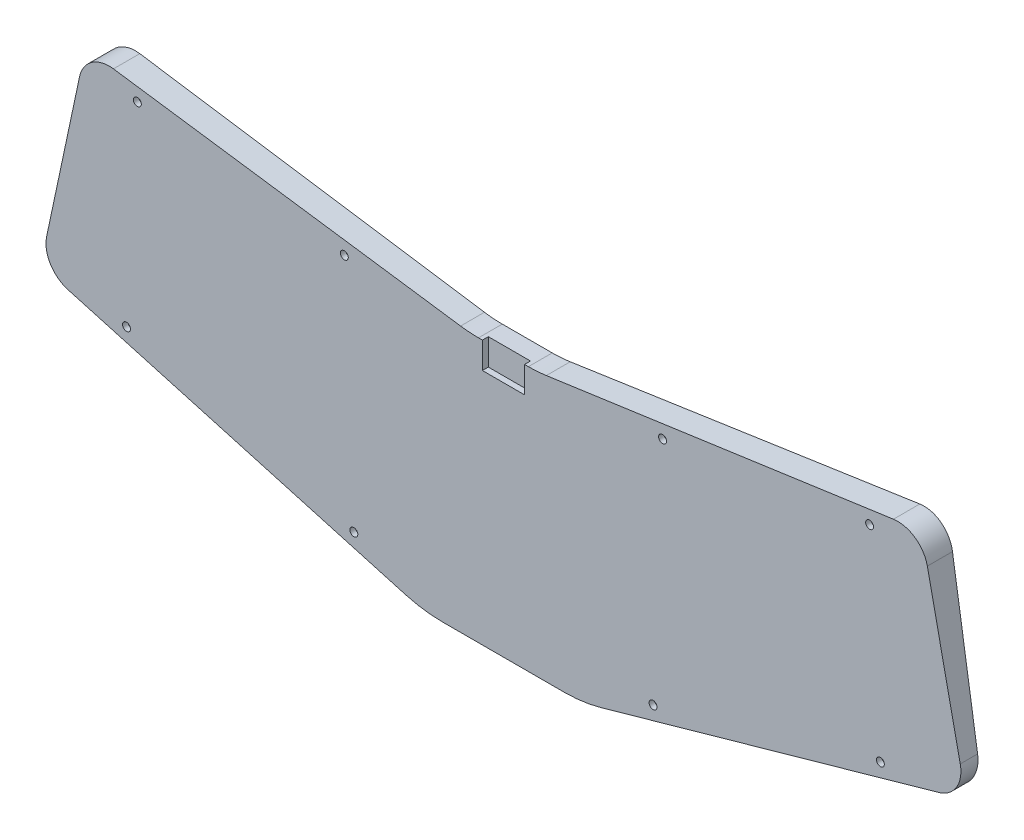
SolidWorks part; units mm, degrees
ref_plane "Front Plane" through (0, 0, 0) normal (0, 0, 1) x (1, 0, 0)
ref_plane "Top Plane" through (0, 0, 0) normal (0, 1, 0) x (1, 0, 0)
ref_plane "Right Plane" through (0, 0, 0) normal (1, 0, 0) x (0, 0, -1)
sketch "Model" plane through (0, 0, 0) normal (0, 0, 1) x (1, 0, 0)
  line L0 (7.1929, 63.9009) -> (19.4198, 61.302)
  line L1 (19.9974, 60.4125) -> (17.3986, 48.1856)
  line L2 (16.509, 47.6079) -> (4.2822, 50.2068)
  line L3 (3.7045, 51.0964) -> (6.3034, 63.3232)
  line L4 (3.2426, 45.3161) -> (15.4694, 42.7172)
  line L5 (16.0471, 41.8276) -> (13.4482, 29.6008)
  line L6 (12.5587, 29.0231) -> (0.3318, 31.622)
  line L7 (-0.2458, 32.5116) -> (2.3531, 44.7384)
  line L8 (-0.7077, 26.7313) -> (11.5191, 24.1324)
  line L9 (12.0968, 23.2428) -> (9.4979, 11.016)
  line L10 (8.6084, 10.4383) -> (-3.6185, 13.0372)
  line L11 (-4.1962, 13.9268) -> (-1.5973, 26.1536)
  line L12 (26.1936, 61.9069) -> (38.4204, 59.308)
  line L13 (38.9981, 58.4184) -> (36.3992, 46.1916)
  line L14 (35.5096, 45.6139) -> (23.2828, 48.2128)
  line L15 (22.7051, 49.1023) -> (25.304, 61.3292)
  line L16 (22.2432, 43.3221) -> (34.4701, 40.7232)
  line L17 (35.0478, 39.8336) -> (32.4489, 27.6068)
  line L18 (31.5593, 27.0291) -> (19.3325, 29.628)
  line L19 (18.7548, 30.5175) -> (21.3537, 42.7444)
  line L20 (18.2929, 24.7373) -> (30.5198, 22.1384)
  line L21 (31.0974, 21.2488) -> (28.4985, 9.022)
  line L22 (27.609, 8.4443) -> (15.3821, 11.0432)
  line L23 (14.8045, 11.9327) -> (17.4034, 24.1596)
  line L24 (45.2981, 60.4019) -> (57.525, 57.803)
  line L25 (58.1027, 56.9135) -> (55.5038, 44.6866)
  line L26 (54.6142, 44.109) -> (42.3874, 46.7078)
  line L27 (41.8097, 47.5974) -> (44.4086, 59.8242)
  line L28 (41.3478, 41.8171) -> (53.5747, 39.2182)
  line L29 (54.1523, 38.3287) -> (51.5534, 26.1018)
  line L30 (50.6639, 25.5241) -> (38.4371, 28.123)
  line L31 (37.8594, 29.0126) -> (40.4583, 41.2394)
  line L32 (37.3975, 23.2323) -> (49.6243, 20.6334)
  line L33 (50.202, 19.7439) -> (47.6031, 7.517)
  line L34 (46.7136, 6.9393) -> (34.4867, 9.5382)
  line L35 (33.9091, 10.4278) -> (36.5079, 22.6546)
  line L36 (64.4027, 58.897) -> (76.6296, 56.2981)
  line L37 (77.2072, 55.4085) -> (74.6083, 43.1817)
  line L38 (73.7188, 42.604) -> (61.492, 45.2029)
  line L39 (60.9143, 46.0924) -> (63.5132, 58.3193)
  line L40 (60.4524, 40.3122) -> (72.6792, 37.7133)
  line L41 (73.2569, 36.8237) -> (70.658, 24.5969)
  line L42 (69.7685, 24.0192) -> (57.5416, 26.6181)
  line L43 (56.964, 27.5076) -> (59.5629, 39.7345)
  line L44 (56.5021, 21.7274) -> (68.7289, 19.1285)
  line L45 (69.3066, 18.2389) -> (66.7077, 6.0121)
  line L46 (65.8182, 5.4344) -> (53.5913, 8.0333)
  line L47 (53.0136, 8.9228) -> (55.6125, 21.1497)
  line L48 (52.5518, 3.1425) -> (64.7786, 0.5437)
  line L49 (65.3563, -0.3459) -> (62.7574, -12.5727)
  line L50 (61.8678, -13.1504) -> (49.641, -10.5515)
  line L51 (49.0633, -9.662) -> (51.6622, 2.5649)
  line L52 (82.4677, 52.5013) -> (94.6946, 49.9024)
  line L53 (95.2723, 49.0128) -> (92.6734, 36.786)
  line L54 (91.7838, 36.2083) -> (79.557, 38.8072)
  line L55 (78.9793, 39.6967) -> (81.5782, 51.9236)
  line L56 (78.5174, 33.9165) -> (90.7443, 31.3176)
  line L57 (91.3219, 30.428) -> (88.723, 18.2012)
  line L58 (87.8335, 17.6235) -> (75.6067, 20.2224)
  line L59 (75.029, 21.1119) -> (77.6279, 33.3388)
  line L60 (74.5671, 15.3317) -> (86.7939, 12.7328)
  line L61 (87.3716, 11.8432) -> (84.7727, -0.3836)
  line L62 (83.8832, -0.9613) -> (71.6563, 1.6376)
  line L63 (71.0787, 2.5271) -> (73.6776, 14.754)
  line L64 (101.4684, 50.5072) -> (113.6952, 47.9083)
  line L65 (114.2729, 47.0188) -> (111.674, 34.792)
  line L66 (110.7845, 34.2143) -> (98.5576, 36.8132)
  line L67 (97.9799, 37.7027) -> (100.5788, 49.9296)
  line L68 (97.5181, 31.9224) -> (109.7449, 29.3235)
  line L69 (110.3226, 28.434) -> (107.7237, 16.2072)
  line L70 (106.8341, 15.6295) -> (94.6073, 18.2284)
  line L71 (94.0296, 19.1179) -> (96.6285, 31.3448)
  line L72 (93.5677, 13.3376) -> (105.7946, 10.7387)
  line L73 (106.3723, 9.8492) -> (103.7734, -2.3777)
  line L74 (102.8838, -2.9553) -> (90.657, -0.3564)
  line L75 (90.0793, 0.5331) -> (92.6782, 12.76)
  line L76 (134.1052, 48.9374) -> (131.5063, 36.7105)
  line L77 (130.6167, 36.1328) -> (118.3899, 38.7317)
  line L78 (117.8122, 39.6213) -> (120.4111, 51.8481)
  line L79 (117.3503, 33.841) -> (129.5772, 31.2421)
  line L80 (130.1548, 30.3526) -> (127.556, 18.1257)
  line L81 (126.6664, 17.548) -> (114.4396, 20.1469)
  line L82 (113.8619, 21.0365) -> (116.4608, 33.2633)
  line L83 (113.4, 15.2562) -> (125.6268, 12.6573)
  line L84 (126.2045, 11.7678) -> (123.6056, -0.4591)
  line L85 (122.7161, -1.0368) -> (110.4892, 1.5621)
  line L86 (109.9116, 2.4517) -> (112.5105, 14.6785)
  line L87 (70.6168, -3.2531) -> (82.8436, -5.852)
  line L88 (83.4213, -6.7416) -> (80.8224, -18.9684)
  line L89 (79.9329, -19.5461) -> (67.706, -16.9472)
  line L90 (67.1283, -16.0577) -> (69.7272, -3.8308)
  line L91 (89.6174, -5.2472) -> (101.8443, -7.8461)
  line L92 (102.4219, -8.7356) -> (99.823, -20.9625)
  line L93 (98.9335, -21.5401) -> (86.7066, -18.9412)
  line L94 (86.129, -18.0517) -> (88.7279, -5.8248)
  line L95 (117.654, -29.3648) -> (112.0852, -26.5274)
  line L96 (111.7574, -25.5186) -> (117.4323, -14.381)
  line L97 (118.4411, -14.0533) -> (129.5787, -19.7282)
  line L98 (129.9064, -20.7369) -> (124.2315, -31.8745)
  line L99 (123.2228, -32.2023) -> (117.654, -29.3648)
  line L100 (112.629, -33.5493) -> (124.2783, -36.8388)
  line L101 (137.0504, -38.6074) -> (160.1264, -38.6074)
  line L102 (160.1264, -38.6074) -> (183.2025, -38.6074)
  line L103 (195.9746, -36.8388) -> (207.6239, -33.5493)
  line L104 (226.4824, -28.2242) -> (271.949, -15.3856)
  line L105 (271.949, -15.3856) -> (293.9202, -9.1816)
  line L106 (210.7632, 57.9332) -> (177.0346, 53.1572)
  line L107 (169.604, 52.6338) -> (150.6488, 52.6338)
  line L108 (143.2182, 53.1572) -> (109.4896, 57.9332)
  line L109 (90.0873, 60.6806) -> (30.9176, 69.0589)
  line L110 (289.3352, 69.0589) -> (230.1656, 60.6806)
  line L111 (26.3327, -9.1816) -> (48.3039, -15.3856)
  line L112 (48.3039, -15.3856) -> (93.7705, -28.2242)
  line L113 (312.7787, -3.8564) -> (324.1811, -0.6367)
  line L114 (-2.1254, 39.3007) -> (3.622, 66.34)
  line L115 (-2.1254, 39.3007) -> (-8.8731, 7.5553)
  line L116 (13.8071, 71.4818) -> (11.4504, 71.8155)
  line L117 (-3.9283, -0.6367) -> (7.4742, -3.8564)
  line L118 (306.4458, 71.4818) -> (308.8024, 71.8155)
  line L119 (322.3782, 39.3007) -> (329.1259, 7.5553)
  line L120 (322.3782, 39.3007) -> (316.6308, 66.34)
  line L121 (121.3006, 52.4258) -> (133.5275, 49.8269)
  line L122 (313.0599, 63.9009) -> (300.8331, 61.302)
  line L123 (300.2554, 60.4125) -> (302.8543, 48.1856)
  line L124 (303.7438, 47.6079) -> (315.9707, 50.2068)
  line L125 (316.5483, 51.0964) -> (313.9494, 63.3232)
  line L126 (317.0102, 45.3161) -> (304.7834, 42.7172)
  line L127 (304.2057, 41.8276) -> (306.8046, 29.6008)
  line L128 (307.6941, 29.0231) -> (319.921, 31.622)
  line L129 (320.4987, 32.5116) -> (317.8998, 44.7384)
  line L130 (320.9605, 26.7313) -> (308.7337, 24.1324)
  line L131 (308.156, 23.2428) -> (310.7549, 11.016)
  line L132 (311.6445, 10.4383) -> (323.8713, 13.0372)
  line L133 (324.449, 13.9268) -> (321.8501, 26.1536)
  line L134 (294.0593, 61.9069) -> (281.8324, 59.308)
  line L135 (281.2548, 58.4184) -> (283.8536, 46.1916)
  line L136 (284.7432, 45.6139) -> (296.97, 48.2128)
  line L137 (297.5477, 49.1023) -> (294.9488, 61.3292)
  line L138 (298.0096, 43.3221) -> (285.7828, 40.7232)
  line L139 (285.2051, 39.8336) -> (287.804, 27.6068)
  line L140 (288.6935, 27.0291) -> (300.9204, 29.628)
  line L141 (301.498, 30.5175) -> (298.8991, 42.7444)
  line L142 (301.9599, 24.7373) -> (289.7331, 22.1384)
  line L143 (289.1554, 21.2488) -> (291.7543, 9.022)
  line L144 (292.6438, 8.4443) -> (304.8707, 11.0432)
  line L145 (305.4484, 11.9327) -> (302.8495, 24.1596)
  line L146 (274.9547, 60.4019) -> (262.7278, 57.803)
  line L147 (262.1502, 56.9135) -> (264.7491, 44.6866)
  line L148 (265.6386, 44.109) -> (277.8655, 46.7078)
  line L149 (278.4431, 47.5974) -> (275.8442, 59.8242)
  line L150 (278.905, 41.8171) -> (266.6782, 39.2182)
  line L151 (266.1005, 38.3287) -> (268.6994, 26.1018)
  line L152 (269.5889, 25.5241) -> (281.8158, 28.123)
  line L153 (282.3935, 29.0126) -> (279.7946, 41.2394)
  line L154 (282.8553, 23.2323) -> (270.6285, 20.6334)
  line L155 (270.0508, 19.7439) -> (272.6497, 7.517)
  line L156 (273.5393, 6.9393) -> (285.7661, 9.5382)
  line L157 (286.3438, 10.4278) -> (283.7449, 22.6546)
  line L158 (255.8501, 58.897) -> (243.6233, 56.2981)
  line L159 (243.0456, 55.4085) -> (245.6445, 43.1817)
  line L160 (246.534, 42.604) -> (258.7609, 45.2029)
  line L161 (259.3385, 46.0924) -> (256.7397, 58.3193)
  line L162 (259.8004, 40.3122) -> (247.5736, 37.7133)
  line L163 (246.9959, 36.8237) -> (249.5948, 24.5969)
  line L164 (250.4843, 24.0192) -> (262.7112, 26.6181)
  line L165 (263.2889, 27.5076) -> (260.69, 39.7345)
  line L166 (263.7508, 21.7274) -> (251.5239, 19.1285)
  line L167 (250.9462, 18.2389) -> (253.5451, 6.0121)
  line L168 (254.4347, 5.4344) -> (266.6615, 8.0333)
  line L169 (267.2392, 8.9228) -> (264.6403, 21.1497)
  line L170 (267.7011, 3.1425) -> (255.4742, 0.5437)
  line L171 (254.8966, -0.3459) -> (257.4954, -12.5727)
  line L172 (258.385, -13.1504) -> (270.6118, -10.5515)
  line L173 (271.1895, -9.662) -> (268.5906, 2.5649)
  line L174 (237.7851, 52.5013) -> (225.5582, 49.9024)
  line L175 (224.9806, 49.0128) -> (227.5795, 36.786)
  line L176 (228.469, 36.2083) -> (240.6958, 38.8072)
  line L177 (241.2735, 39.6967) -> (238.6746, 51.9236)
  line L178 (241.7354, 33.9165) -> (229.5086, 31.3176)
  line L179 (228.9309, 30.428) -> (231.5298, 18.2012)
  line L180 (232.4193, 17.6235) -> (244.6462, 20.2224)
  line L181 (245.2238, 21.1119) -> (242.6249, 33.3388)
  line L182 (245.6857, 15.3317) -> (233.4589, 12.7328)
  line L183 (232.8812, 11.8432) -> (235.4801, -0.3836)
  line L184 (236.3696, -0.9613) -> (248.5965, 1.6376)
  line L185 (249.1742, 2.5271) -> (246.5753, 14.754)
  line L186 (218.7845, 50.5072) -> (206.5576, 47.9083)
  line L187 (205.9799, 47.0188) -> (208.5788, 34.792)
  line L188 (209.4684, 34.2143) -> (221.6952, 36.8132)
  line L189 (222.2729, 37.7027) -> (219.674, 49.9296)
  line L190 (222.7348, 31.9224) -> (210.5079, 29.3235)
  line L191 (209.9303, 28.434) -> (212.5292, 16.2072)
  line L192 (213.4187, 15.6295) -> (225.6455, 18.2284)
  line L193 (226.2232, 19.1179) -> (223.6243, 31.3448)
  line L194 (226.6851, 13.3376) -> (214.4583, 10.7387)
  line L195 (213.8806, 9.8492) -> (216.4795, -2.3777)
  line L196 (217.369, -2.9553) -> (229.5959, -0.3564)
  line L197 (230.1735, 0.5331) -> (227.5746, 12.76)
  line L198 (186.1477, 48.9374) -> (188.7466, 36.7105)
  line L199 (189.6361, 36.1328) -> (201.8629, 38.7317)
  line L200 (202.4406, 39.6213) -> (199.8417, 51.8481)
  line L201 (202.9025, 33.841) -> (190.6757, 31.2421)
  line L202 (190.098, 30.3526) -> (192.6969, 18.1257)
  line L203 (193.5864, 17.548) -> (205.8133, 20.1469)
  line L204 (206.3909, 21.0365) -> (203.792, 33.2633)
  line L205 (206.8528, 15.2562) -> (194.626, 12.6573)
  line L206 (194.0483, 11.7678) -> (196.6472, -0.4591)
  line L207 (197.5367, -1.0368) -> (209.7636, 1.5621)
  line L208 (210.3413, 2.4517) -> (207.7424, 14.6785)
  line L209 (249.636, -3.2531) -> (237.4092, -5.852)
  line L210 (236.8315, -6.7416) -> (239.4304, -18.9684)
  line L211 (240.32, -19.5461) -> (252.5468, -16.9472)
  line L212 (253.1245, -16.0577) -> (250.5256, -3.8308)
  line L213 (230.6354, -5.2472) -> (218.4086, -7.8461)
  line L214 (217.8309, -8.7356) -> (220.4298, -20.9625)
  line L215 (221.3193, -21.5401) -> (233.5462, -18.9412)
  line L216 (234.1239, -18.0517) -> (231.525, -5.8248)
  line L217 (202.5988, -29.3648) -> (208.1676, -26.5274)
  line L218 (208.4954, -25.5186) -> (202.8205, -14.381)
  line L219 (201.8118, -14.0533) -> (190.6742, -19.7282)
  line L220 (190.3464, -20.7369) -> (196.0213, -31.8745)
  line L221 (197.03, -32.2023) -> (202.5988, -29.3648)
  line L222 (198.9522, 52.4258) -> (186.7253, 49.8269)
  line L223 (169.604, 55.6338) -> (150.6488, 55.6338)
  line L224 (143.6388, 56.1276) -> (11.8711, 74.7858)
  line L225 (0.6876, 66.9637) -> (-5.0598, 39.9244)
  line L226 (-5.0598, 39.9244) -> (-11.8075, 8.179)
  line L227 (-4.7435, -3.5238) -> (47.4886, -18.2727)
  line L228 (47.4886, -18.2727) -> (123.463, -39.7259)
  line L229 (137.0504, -41.6074) -> (160.1264, -41.6074)
  line L230 (160.1264, -41.6074) -> (183.2025, -41.6074)
  line L231 (196.7898, -39.7259) -> (272.7642, -18.2727)
  line L232 (272.7642, -18.2727) -> (324.9963, -3.5238)
  line L233 (332.0603, 8.179) -> (325.3126, 39.9244)
  line L234 (325.3126, 39.9244) -> (319.5653, 66.9637)
  line L235 (308.3818, 74.7858) -> (176.614, 56.1276)
  line L236 (169.604, 57.1338) -> (150.6488, 57.1338)
  line L237 (143.8491, 57.6128) -> (12.0814, 76.271)
  line L238 (-0.7797, 67.2756) -> (-6.527, 40.2363)
  line L239 (-6.527, 40.2363) -> (-13.2747, 8.4909)
  line L240 (-5.1511, -4.9673) -> (47.081, -19.7163)
  line L241 (47.081, -19.7163) -> (123.0554, -41.1694)
  line L242 (137.0504, -43.1074) -> (160.1264, -43.1074)
  line L243 (160.1264, -43.1074) -> (183.2025, -43.1074)
  line L244 (197.1974, -41.1694) -> (273.1718, -19.7163)
  line L245 (273.1718, -19.7163) -> (325.404, -4.9673)
  line L246 (333.5276, 8.4909) -> (326.7799, 40.2363)
  line L247 (326.7799, 40.2363) -> (321.0325, 67.2756)
  line L248 (308.1715, 76.271) -> (176.4037, 57.6128)
  arc A0 (106.6702, -28.8979) -> (101.2821, -27.3764) centre (103.1997, -30.8868) ccw
  arc A1 (93.7705, -28.2242) -> (101.2821, -27.3764) centre (96.4879, -18.6005) ccw
  arc A2 (106.6702, -28.8979) -> (112.629, -33.5493) centre (115.3464, -23.9256) ccw
  circle A3 centre (103.3356, -30.4056) radius 1.5
  arc A4 (207.6239, -33.5493) -> (213.5826, -28.8979) centre (204.9064, -23.9256) ccw
  arc A5 (218.9708, -27.3764) -> (226.4824, -28.2242) centre (223.7649, -18.6005) ccw
  arc A6 (218.9708, -27.3764) -> (213.5826, -28.8979) centre (217.0531, -30.8868) ccw
  circle A7 centre (216.9173, -30.4056) radius 1.5
  arc A8 (218.0932, 56.0855) -> (223.6367, 56.8704) centre (220.4644, 59.3069) ccw
  arc A9 (96.6161, 56.8704) -> (102.1596, 56.0855) centre (99.7884, 59.3069) ccw
  arc A10 (109.4896, 57.9332) -> (102.1596, 56.0855) centre (108.0876, 48.032) ccw
  arc A11 (96.6161, 56.8704) -> (90.0873, 60.6806) centre (88.6852, 50.7793) ccw
  arc A12 (218.0932, 56.0855) -> (210.7632, 57.9332) centre (212.1652, 48.032) ccw
  arc A13 (230.1656, 60.6806) -> (223.6367, 56.8704) centre (231.5676, 50.7793) ccw
  circle A14 centre (99.7183, 58.8118) radius 1.5
  circle A15 centre (220.5345, 58.8118) radius 1.5
  arc A16 (305.2671, -3.0086) -> (299.8789, -4.5301) centre (303.3494, -6.519) ccw
  arc A17 (20.3739, -4.5301) -> (14.9858, -3.0086) centre (16.9034, -6.519) ccw
  arc A18 (20.3739, -4.5301) -> (26.3327, -9.1816) centre (29.0501, 0.4421) ccw
  arc A19 (305.2671, -3.0086) -> (312.7787, -3.8564) centre (310.0612, 5.7673) ccw
  arc A20 (293.9202, -9.1816) -> (299.8789, -4.5301) centre (291.2027, 0.4421) ccw
  arc A21 (7.4742, -3.8564) -> (14.9858, -3.0086) centre (10.1916, 5.7673) ccw
  circle A22 centre (17.0393, -6.0378) radius 1.5
  circle A23 centre (303.2135, -6.0378) radius 1.5
  arc A24 (-8.8731, 7.5553) -> (-3.9283, -0.6367) centre (-2.026, 6.0999) ccw
  arc A25 (11.4504, 71.8155) -> (3.622, 66.34) centre (10.469, 64.8846) ccw
  arc A26 (316.6308, 66.34) -> (308.8024, 71.8155) centre (309.7838, 64.8846) ccw
  arc A27 (324.1811, -0.6367) -> (329.1259, 7.5553) centre (322.2789, 6.0999) ccw
  arc A28 (296.6652, 67.2112) -> (302.641, 68.6986) centre (299.0364, 70.4326) ccw
  arc A29 (17.6118, 68.6986) -> (23.5876, 67.2112) centre (21.2165, 70.4326) ccw
  arc A30 (30.9176, 69.0589) -> (23.5876, 67.2112) centre (29.5156, 59.1577) ccw
  arc A31 (17.6118, 68.6986) -> (13.8071, 71.4818) centre (13.106, 66.5312) ccw
  arc A32 (306.4458, 71.4818) -> (302.641, 68.6986) centre (307.1468, 66.5312) ccw
  arc A33 (296.6652, 67.2112) -> (289.3352, 69.0589) centre (290.7372, 59.1577) ccw
  circle A34 centre (299.1065, 69.9376) radius 1.5
  circle A35 centre (21.1464, 69.9376) radius 1.5
  arc A36 (3.7045, 51.0964) -> (4.2822, 50.2068) centre (4.4381, 50.9404) ccw
  arc A37 (7.1929, 63.9009) -> (6.3034, 63.3232) centre (7.037, 63.1673) ccw
  arc A38 (19.9974, 60.4125) -> (19.4198, 61.302) centre (19.2638, 60.5684) ccw
  arc A39 (16.509, 47.6079) -> (17.3986, 48.1856) centre (16.6649, 48.3415) ccw
  arc A40 (3.2426, 45.3161) -> (2.3531, 44.7384) centre (3.0867, 44.5825) ccw
  arc A41 (-0.2458, 32.5116) -> (0.3318, 31.622) centre (0.4878, 32.3556) ccw
  arc A42 (12.5587, 29.0231) -> (13.4482, 29.6008) centre (12.7146, 29.7567) ccw
  arc A43 (16.0471, 41.8276) -> (15.4694, 42.7172) centre (15.3135, 41.9836) ccw
  arc A44 (-0.7077, 26.7313) -> (-1.5973, 26.1536) centre (-0.8637, 25.9977) ccw
  arc A45 (-4.1962, 13.9268) -> (-3.6185, 13.0372) centre (-3.4625, 13.7708) ccw
  arc A46 (8.6084, 10.4383) -> (9.4979, 11.016) centre (8.7643, 11.1719) ccw
  arc A47 (12.0968, 23.2428) -> (11.5191, 24.1324) centre (11.3632, 23.3988) ccw
  arc A48 (14.8045, 11.9327) -> (15.3821, 11.0432) centre (15.5381, 11.7768) ccw
  arc A49 (27.609, 8.4443) -> (28.4985, 9.022) centre (27.7649, 9.1779) ccw
  arc A50 (31.0974, 21.2488) -> (30.5198, 22.1384) centre (30.3638, 21.4048) ccw
  arc A51 (18.2929, 24.7373) -> (17.4034, 24.1596) centre (18.137, 24.0036) ccw
  arc A52 (18.7548, 30.5175) -> (19.3325, 29.628) centre (19.4884, 30.3616) ccw
  arc A53 (31.5593, 27.0291) -> (32.4489, 27.6068) centre (31.7152, 27.7627) ccw
  arc A54 (35.0478, 39.8336) -> (34.4701, 40.7232) centre (34.3141, 39.9896) ccw
  arc A55 (22.2432, 43.3221) -> (21.3537, 42.7444) centre (22.0873, 42.5885) ccw
  arc A56 (22.7051, 49.1023) -> (23.2828, 48.2128) centre (23.4387, 48.9464) ccw
  arc A57 (35.5096, 45.6139) -> (36.3992, 46.1916) centre (35.6656, 46.3475) ccw
  arc A58 (38.9981, 58.4184) -> (38.4204, 59.308) centre (38.2645, 58.5744) ccw
  arc A59 (26.1936, 61.9069) -> (25.304, 61.3292) centre (26.0376, 61.1733) ccw
  arc A60 (33.9091, 10.4278) -> (34.4867, 9.5382) centre (34.6427, 10.2718) ccw
  arc A61 (37.3975, 23.2323) -> (36.5079, 22.6546) centre (37.2416, 22.4987) ccw
  arc A62 (50.202, 19.7439) -> (49.6243, 20.6334) centre (49.4684, 19.8998) ccw
  arc A63 (46.7136, 6.9393) -> (47.6031, 7.517) centre (46.8695, 7.673) ccw
  arc A64 (50.6639, 25.5241) -> (51.5534, 26.1018) centre (50.8198, 26.2578) ccw
  arc A65 (37.8594, 29.0126) -> (38.4371, 28.123) centre (38.593, 28.8567) ccw
  arc A66 (41.3478, 41.8171) -> (40.4583, 41.2394) centre (41.1919, 41.0835) ccw
  arc A67 (54.1523, 38.3287) -> (53.5747, 39.2182) centre (53.4187, 38.4846) ccw
  arc A68 (54.6142, 44.109) -> (55.5038, 44.6866) centre (54.7702, 44.8426) ccw
  arc A69 (41.8097, 47.5974) -> (42.3874, 46.7078) centre (42.5433, 47.4415) ccw
  arc A70 (45.2981, 60.4019) -> (44.4086, 59.8242) centre (45.1422, 59.6683) ccw
  arc A71 (58.1027, 56.9135) -> (57.525, 57.803) centre (57.369, 57.0694) ccw
  arc A72 (56.964, 27.5076) -> (57.5416, 26.6181) centre (57.6976, 27.3517) ccw
  arc A73 (60.4524, 40.3122) -> (59.5629, 39.7345) centre (60.2965, 39.5785) ccw
  arc A74 (73.2569, 36.8237) -> (72.6792, 37.7133) centre (72.5233, 36.9797) ccw
  arc A75 (69.7685, 24.0192) -> (70.658, 24.5969) centre (69.9244, 24.7528) ccw
  arc A76 (60.9143, 46.0924) -> (61.492, 45.2029) centre (61.6479, 45.9365) ccw
  arc A77 (73.7188, 42.604) -> (74.6083, 43.1817) centre (73.8747, 43.3376) ccw
  arc A78 (77.2072, 55.4085) -> (76.6296, 56.2981) centre (76.4736, 55.5645) ccw
  arc A79 (64.4027, 58.897) -> (63.5132, 58.3193) centre (64.2468, 58.1634) ccw
  arc A80 (53.0136, 8.9228) -> (53.5913, 8.0333) centre (53.7472, 8.7669) ccw
  arc A81 (56.5021, 21.7274) -> (55.6125, 21.1497) centre (56.3461, 20.9937) ccw
  arc A82 (69.3066, 18.2389) -> (68.7289, 19.1285) centre (68.573, 18.3948) ccw
  arc A83 (65.8182, 5.4344) -> (66.7077, 6.0121) centre (65.9741, 6.168) ccw
  arc A84 (49.0633, -9.662) -> (49.641, -10.5515) centre (49.7969, -9.8179) ccw
  arc A85 (52.5518, 3.1425) -> (51.6622, 2.5649) centre (52.3958, 2.4089) ccw
  arc A86 (65.3563, -0.3459) -> (64.7786, 0.5437) centre (64.6227, -0.19) ccw
  arc A87 (61.8678, -13.1504) -> (62.7574, -12.5727) centre (62.0238, -12.4168) ccw
  arc A88 (67.1283, -16.0577) -> (67.706, -16.9472) centre (67.8619, -16.2136) ccw
  arc A89 (70.6168, -3.2531) -> (69.7272, -3.8308) centre (70.4608, -3.9868) ccw
  arc A90 (83.4213, -6.7416) -> (82.8436, -5.852) centre (82.6877, -6.5856) ccw
  arc A91 (79.9329, -19.5461) -> (80.8224, -18.9684) centre (80.0888, -18.8125) ccw
  arc A92 (71.0787, 2.5271) -> (71.6563, 1.6376) centre (71.8123, 2.3712) ccw
  arc A93 (83.8832, -0.9613) -> (84.7727, -0.3836) centre (84.0391, -0.2277) ccw
  arc A94 (87.3716, 11.8432) -> (86.7939, 12.7328) centre (86.638, 11.9992) ccw
  arc A95 (74.5671, 15.3317) -> (73.6776, 14.754) centre (74.4112, 14.5981) ccw
  arc A96 (75.029, 21.1119) -> (75.6067, 20.2224) centre (75.7626, 20.956) ccw
  arc A97 (87.8335, 17.6235) -> (88.723, 18.2012) centre (87.9894, 18.3571) ccw
  arc A98 (91.3219, 30.428) -> (90.7443, 31.3176) centre (90.5883, 30.584) ccw
  arc A99 (78.5174, 33.9165) -> (77.6279, 33.3388) centre (78.3615, 33.1829) ccw
  arc A100 (78.9793, 39.6967) -> (79.557, 38.8072) centre (79.7129, 39.5408) ccw
  arc A101 (82.4677, 52.5013) -> (81.5782, 51.9236) centre (82.3118, 51.7677) ccw
  arc A102 (95.2723, 49.0128) -> (94.6946, 49.9024) centre (94.5387, 49.1688) ccw
  arc A103 (91.7838, 36.2083) -> (92.6734, 36.786) centre (91.9398, 36.9419) ccw
  arc A104 (97.9799, 37.7027) -> (98.5576, 36.8132) centre (98.7135, 37.5468) ccw
  arc A105 (101.4684, 50.5072) -> (100.5788, 49.9296) centre (101.3124, 49.7736) ccw
  arc A106 (114.2729, 47.0188) -> (113.6952, 47.9083) centre (113.5393, 47.1747) ccw
  arc A107 (110.7845, 34.2143) -> (111.674, 34.792) centre (110.9404, 34.9479) ccw
  arc A108 (97.5181, 31.9224) -> (96.6285, 31.3448) centre (97.3621, 31.1888) ccw
  arc A109 (110.3226, 28.434) -> (109.7449, 29.3235) centre (109.589, 28.5899) ccw
  arc A110 (106.8341, 15.6295) -> (107.7237, 16.2072) centre (106.9901, 16.3631) ccw
  arc A111 (94.0296, 19.1179) -> (94.6073, 18.2284) centre (94.7632, 18.962) ccw
  arc A112 (93.5677, 13.3376) -> (92.6782, 12.76) centre (93.4118, 12.604) ccw
  arc A113 (106.3723, 9.8492) -> (105.7946, 10.7387) centre (105.6386, 10.0051) ccw
  arc A114 (102.8838, -2.9553) -> (103.7734, -2.3777) centre (103.0397, -2.2217) ccw
  arc A115 (90.0793, 0.5331) -> (90.657, -0.3564) centre (90.8129, 0.3772) ccw
  arc A116 (89.6174, -5.2472) -> (88.7279, -5.8248) centre (89.4615, -5.9808) ccw
  arc A117 (102.4219, -8.7356) -> (101.8443, -7.8461) centre (101.6883, -8.5797) ccw
  arc A118 (98.9335, -21.5401) -> (99.823, -20.9625) centre (99.0894, -20.8065) ccw
  arc A119 (86.129, -18.0517) -> (86.7066, -18.9412) centre (86.8626, -18.2076) ccw
  arc A120 (111.7574, -25.5186) -> (112.0852, -26.5274) centre (112.4257, -25.8591) ccw
  arc A121 (118.4411, -14.0533) -> (117.4323, -14.381) centre (118.1006, -14.7215) ccw
  arc A122 (129.9064, -20.7369) -> (129.5787, -19.7282) centre (129.2382, -20.3964) ccw
  arc A123 (123.2228, -32.2023) -> (124.2315, -31.8745) centre (123.5633, -31.534) ccw
  arc A124 (109.9116, 2.4517) -> (110.4892, 1.5621) centre (110.6452, 2.2957) ccw
  arc A125 (122.7161, -1.0368) -> (123.6056, -0.4591) centre (122.872, -0.3032) ccw
  arc A126 (126.2045, 11.7678) -> (125.6268, 12.6573) centre (125.4709, 11.9237) ccw
  arc A127 (113.4, 15.2562) -> (112.5105, 14.6785) centre (113.2441, 14.5226) ccw
  arc A128 (113.8619, 21.0365) -> (114.4396, 20.1469) centre (114.5955, 20.8805) ccw
  arc A129 (126.6664, 17.548) -> (127.556, 18.1257) centre (126.8223, 18.2817) ccw
  arc A130 (130.1548, 30.3526) -> (129.5772, 31.2421) centre (129.4212, 30.5085) ccw
  arc A131 (117.3503, 33.841) -> (116.4608, 33.2633) centre (117.1944, 33.1074) ccw
  arc A132 (117.8122, 39.6213) -> (118.3899, 38.7317) centre (118.5458, 39.4654) ccw
  arc A133 (130.6167, 36.1328) -> (131.5063, 36.7105) centre (130.7727, 36.8665) ccw
  arc A134 (134.1052, 48.9374) -> (133.5275, 49.8269) centre (133.3716, 49.0933) ccw
  arc A135 (121.3006, 52.4258) -> (120.4111, 51.8481) centre (121.1447, 51.6922) ccw
  arc A136 (313.9494, 63.3232) -> (313.0599, 63.9009) centre (313.2158, 63.1673) ccw
  arc A137 (300.8331, 61.302) -> (300.2554, 60.4125) centre (300.989, 60.5684) ccw
  arc A138 (302.8543, 48.1856) -> (303.7438, 47.6079) centre (303.5879, 48.3415) ccw
  arc A139 (315.9707, 50.2068) -> (316.5483, 51.0964) centre (315.8147, 50.9404) ccw
  arc A140 (317.8998, 44.7384) -> (317.0102, 45.3161) centre (317.1662, 44.5825) ccw
  arc A141 (304.7834, 42.7172) -> (304.2057, 41.8276) centre (304.9393, 41.9836) ccw
  arc A142 (306.8046, 29.6008) -> (307.6941, 29.0231) centre (307.5382, 29.7567) ccw
  arc A143 (319.921, 31.622) -> (320.4987, 32.5116) centre (319.7651, 32.3556) ccw
  arc A144 (321.8501, 26.1536) -> (320.9605, 26.7313) centre (321.1165, 25.9977) ccw
  arc A145 (308.7337, 24.1324) -> (308.156, 23.2428) centre (308.8896, 23.3988) ccw
  arc A146 (310.7549, 11.016) -> (311.6445, 10.4383) centre (311.4885, 11.1719) ccw
  arc A147 (323.8713, 13.0372) -> (324.449, 13.9268) centre (323.7154, 13.7708) ccw
  arc A148 (294.9488, 61.3292) -> (294.0593, 61.9069) centre (294.2152, 61.1733) ccw
  arc A149 (281.8324, 59.308) -> (281.2548, 58.4184) centre (281.9884, 58.5744) ccw
  arc A150 (283.8536, 46.1916) -> (284.7432, 45.6139) centre (284.5873, 46.3475) ccw
  arc A151 (296.97, 48.2128) -> (297.5477, 49.1023) centre (296.8141, 48.9464) ccw
  arc A152 (298.8991, 42.7444) -> (298.0096, 43.3221) centre (298.1655, 42.5885) ccw
  arc A153 (285.7828, 40.7232) -> (285.2051, 39.8336) centre (285.9387, 39.9896) ccw
  arc A154 (287.804, 27.6068) -> (288.6935, 27.0291) centre (288.5376, 27.7627) ccw
  arc A155 (300.9204, 29.628) -> (301.498, 30.5175) centre (300.7644, 30.3616) ccw
  arc A156 (302.8495, 24.1596) -> (301.9599, 24.7373) centre (302.1159, 24.0036) ccw
  arc A157 (289.7331, 22.1384) -> (289.1554, 21.2488) centre (289.889, 21.4048) ccw
  arc A158 (291.7543, 9.022) -> (292.6438, 8.4443) centre (292.4879, 9.1779) ccw
  arc A159 (304.8707, 11.0432) -> (305.4484, 11.9327) centre (304.7147, 11.7768) ccw
  arc A160 (262.7278, 57.803) -> (262.1502, 56.9135) centre (262.8838, 57.0694) ccw
  arc A161 (275.8442, 59.8242) -> (274.9547, 60.4019) centre (275.1106, 59.6683) ccw
  arc A162 (264.7491, 44.6866) -> (265.6386, 44.109) centre (265.4827, 44.8426) ccw
  arc A163 (277.8655, 46.7078) -> (278.4431, 47.5974) centre (277.7095, 47.4415) ccw
  arc A164 (266.6782, 39.2182) -> (266.1005, 38.3287) centre (266.8341, 38.4846) ccw
  arc A165 (279.7946, 41.2394) -> (278.905, 41.8171) centre (279.0609, 41.0835) ccw
  arc A166 (268.6994, 26.1018) -> (269.5889, 25.5241) centre (269.433, 26.2578) ccw
  arc A167 (281.8158, 28.123) -> (282.3935, 29.0126) centre (281.6598, 28.8567) ccw
  arc A168 (270.6285, 20.6334) -> (270.0508, 19.7439) centre (270.7844, 19.8998) ccw
  arc A169 (283.7449, 22.6546) -> (282.8553, 23.2323) centre (283.0113, 22.4987) ccw
  arc A170 (272.6497, 7.517) -> (273.5393, 6.9393) centre (273.3833, 7.673) ccw
  arc A171 (285.7661, 9.5382) -> (286.3438, 10.4278) centre (285.6102, 10.2718) ccw
  arc A172 (256.7397, 58.3193) -> (255.8501, 58.897) centre (256.006, 58.1634) ccw
  arc A173 (243.6233, 56.2981) -> (243.0456, 55.4085) centre (243.7792, 55.5645) ccw
  arc A174 (245.6445, 43.1817) -> (246.534, 42.604) centre (246.3781, 43.3376) ccw
  arc A175 (258.7609, 45.2029) -> (259.3385, 46.0924) centre (258.6049, 45.9365) ccw
  arc A176 (247.5736, 37.7133) -> (246.9959, 36.8237) centre (247.7295, 36.9797) ccw
  arc A177 (260.69, 39.7345) -> (259.8004, 40.3122) centre (259.9564, 39.5785) ccw
  arc A178 (249.5948, 24.5969) -> (250.4843, 24.0192) centre (250.3284, 24.7528) ccw
  arc A179 (262.7112, 26.6181) -> (263.2889, 27.5076) centre (262.5553, 27.3517) ccw
  arc A180 (251.5239, 19.1285) -> (250.9462, 18.2389) centre (251.6798, 18.3948) ccw
  arc A181 (253.5451, 6.0121) -> (254.4347, 5.4344) centre (254.2787, 6.168) ccw
  arc A182 (264.6403, 21.1497) -> (263.7508, 21.7274) centre (263.9067, 20.9937) ccw
  arc A183 (266.6615, 8.0333) -> (267.2392, 8.9228) centre (266.5056, 8.7669) ccw
  arc A184 (255.4742, 0.5437) -> (254.8966, -0.3459) centre (255.6302, -0.19) ccw
  arc A185 (257.4954, -12.5727) -> (258.385, -13.1504) centre (258.2291, -12.4168) ccw
  arc A186 (268.5906, 2.5649) -> (267.7011, 3.1425) centre (267.857, 2.4089) ccw
  arc A187 (270.6118, -10.5515) -> (271.1895, -9.662) centre (270.4559, -9.8179) ccw
  arc A188 (225.5582, 49.9024) -> (224.9806, 49.0128) centre (225.7142, 49.1688) ccw
  arc A189 (238.6746, 51.9236) -> (237.7851, 52.5013) centre (237.941, 51.7677) ccw
  arc A190 (227.5795, 36.786) -> (228.469, 36.2083) centre (228.3131, 36.9419) ccw
  arc A191 (240.6958, 38.8072) -> (241.2735, 39.6967) centre (240.5399, 39.5408) ccw
  arc A192 (242.6249, 33.3388) -> (241.7354, 33.9165) centre (241.8913, 33.1829) ccw
  arc A193 (229.5086, 31.3176) -> (228.9309, 30.428) centre (229.6645, 30.584) ccw
  arc A194 (231.5298, 18.2012) -> (232.4193, 17.6235) centre (232.2634, 18.3571) ccw
  arc A195 (244.6462, 20.2224) -> (245.2238, 21.1119) centre (244.4902, 20.956) ccw
  arc A196 (246.5753, 14.754) -> (245.6857, 15.3317) centre (245.8417, 14.5981) ccw
  arc A197 (233.4589, 12.7328) -> (232.8812, 11.8432) centre (233.6148, 11.9992) ccw
  arc A198 (235.4801, -0.3836) -> (236.3696, -0.9613) centre (236.2137, -0.2277) ccw
  arc A199 (248.5965, 1.6376) -> (249.1742, 2.5271) centre (248.4406, 2.3712) ccw
  arc A200 (206.5576, 47.9083) -> (205.9799, 47.0188) centre (206.7135, 47.1747) ccw
  arc A201 (219.674, 49.9296) -> (218.7845, 50.5072) centre (218.9404, 49.7736) ccw
  arc A202 (208.5788, 34.792) -> (209.4684, 34.2143) centre (209.3124, 34.9479) ccw
  arc A203 (221.6952, 36.8132) -> (222.2729, 37.7027) centre (221.5393, 37.5468) ccw
  arc A204 (210.5079, 29.3235) -> (209.9303, 28.434) centre (210.6639, 28.5899) ccw
  arc A205 (223.6243, 31.3448) -> (222.7348, 31.9224) centre (222.8907, 31.1888) ccw
  arc A206 (212.5292, 16.2072) -> (213.4187, 15.6295) centre (213.2628, 16.3631) ccw
  arc A207 (225.6455, 18.2284) -> (226.2232, 19.1179) centre (225.4896, 18.962) ccw
  arc A208 (227.5746, 12.76) -> (226.6851, 13.3376) centre (226.841, 12.604) ccw
  arc A209 (216.4795, -2.3777) -> (217.369, -2.9553) centre (217.2131, -2.2217) ccw
  arc A210 (214.4583, 10.7387) -> (213.8806, 9.8492) centre (214.6142, 10.0051) ccw
  arc A211 (229.5959, -0.3564) -> (230.1735, 0.5331) centre (229.4399, 0.3772) ccw
  arc A212 (199.8417, 51.8481) -> (198.9522, 52.4258) centre (199.1081, 51.6922) ccw
  arc A213 (186.7253, 49.8269) -> (186.1477, 48.9374) centre (186.8813, 49.0933) ccw
  arc A214 (188.7466, 36.7105) -> (189.6361, 36.1328) centre (189.4802, 36.8665) ccw
  arc A215 (201.8629, 38.7317) -> (202.4406, 39.6213) centre (201.707, 39.4654) ccw
  arc A216 (203.792, 33.2633) -> (202.9025, 33.841) centre (203.0584, 33.1074) ccw
  arc A217 (190.6757, 31.2421) -> (190.098, 30.3526) centre (190.8316, 30.5085) ccw
  arc A218 (192.6969, 18.1257) -> (193.5864, 17.548) centre (193.4305, 18.2817) ccw
  arc A219 (205.8133, 20.1469) -> (206.3909, 21.0365) centre (205.6573, 20.8805) ccw
  arc A220 (207.7424, 14.6785) -> (206.8528, 15.2562) centre (207.0088, 14.5226) ccw
  arc A221 (194.626, 12.6573) -> (194.0483, 11.7678) centre (194.7819, 11.9237) ccw
  arc A222 (196.6472, -0.4591) -> (197.5367, -1.0368) centre (197.3808, -0.3032) ccw
  arc A223 (209.7636, 1.5621) -> (210.3413, 2.4517) centre (209.6077, 2.2957) ccw
  arc A224 (250.5256, -3.8308) -> (249.636, -3.2531) centre (249.792, -3.9868) ccw
  arc A225 (239.4304, -18.9684) -> (240.32, -19.5461) centre (240.164, -18.8125) ccw
  arc A226 (237.4092, -5.852) -> (236.8315, -6.7416) centre (237.5651, -6.5856) ccw
  arc A227 (252.5468, -16.9472) -> (253.1245, -16.0577) centre (252.3909, -16.2136) ccw
  arc A228 (218.4086, -7.8461) -> (217.8309, -8.7356) centre (218.5645, -8.5797) ccw
  arc A229 (231.525, -5.8248) -> (230.6354, -5.2472) centre (230.7914, -5.9808) ccw
  arc A230 (220.4298, -20.9625) -> (221.3193, -21.5401) centre (221.1634, -20.8065) ccw
  arc A231 (233.5462, -18.9412) -> (234.1239, -18.0517) centre (233.3903, -18.2076) ccw
  arc A232 (208.1676, -26.5274) -> (208.4954, -25.5186) centre (207.8271, -25.8591) ccw
  arc A233 (190.6742, -19.7282) -> (190.3464, -20.7369) centre (191.0147, -20.3964) ccw
  arc A234 (202.8205, -14.381) -> (201.8118, -14.0533) centre (202.1522, -14.7215) ccw
  arc A235 (196.0213, -31.8745) -> (197.03, -32.2023) centre (196.6895, -31.534) ccw
  arc A236 (124.2783, -36.8388) -> (137.0504, -38.6074) centre (137.0504, 8.3926) ccw
  arc A237 (183.2025, -38.6074) -> (195.9746, -36.8388) centre (183.2025, 8.3926) ccw
  arc A238 (169.604, 52.6338) -> (177.0346, 53.1572) centre (169.604, 105.6338) ccw
  arc A239 (143.2182, 53.1572) -> (150.6488, 52.6338) centre (150.6488, 105.6338) ccw
  arc A240 (169.604, 55.6338) -> (176.614, 56.1276) centre (169.604, 105.6338) ccw
  arc A241 (143.6388, 56.1276) -> (150.6488, 55.6338) centre (150.6488, 105.6338) ccw
  arc A242 (11.8711, 74.7858) -> (0.6876, 66.9637) centre (10.469, 64.8846) ccw
  arc A243 (-11.8075, 8.179) -> (-4.7435, -3.5238) centre (-2.026, 6.0999) ccw
  arc A244 (123.463, -39.7259) -> (137.0504, -41.6074) centre (137.0504, 8.3926) ccw
  arc A245 (183.2025, -41.6074) -> (196.7898, -39.7259) centre (183.2025, 8.3926) ccw
  arc A246 (324.9963, -3.5238) -> (332.0603, 8.179) centre (322.2789, 6.0999) ccw
  arc A247 (319.5653, 66.9637) -> (308.3818, 74.7858) centre (309.7838, 64.8846) ccw
  arc A248 (169.604, 57.1338) -> (176.4037, 57.6128) centre (169.604, 105.6338) ccw
  arc A249 (143.8491, 57.6128) -> (150.6488, 57.1338) centre (150.6488, 105.6338) ccw
  arc A250 (12.0814, 76.271) -> (-0.7797, 67.2756) centre (10.469, 64.8846) ccw
  arc A251 (-13.2747, 8.4909) -> (-5.1511, -4.9673) centre (-2.026, 6.0999) ccw
  arc A252 (123.0554, -41.1694) -> (137.0504, -43.1074) centre (137.0504, 8.3926) ccw
  arc A253 (183.2025, -43.1074) -> (197.1974, -41.1694) centre (183.2025, 8.3926) ccw
  arc A254 (325.404, -4.9673) -> (333.5276, 8.4909) centre (322.2789, 6.0999) ccw
  arc A255 (321.0325, 67.2756) -> (308.1715, 76.271) centre (309.7838, 64.8846) ccw
  circle A256 centre (21.1464, 69.9376) radius 2.8
  circle A257 centre (99.7183, 58.8118) radius 2.8
  circle A258 centre (220.5345, 58.8118) radius 2.8
  circle A259 centre (299.1065, 69.9376) radius 2.8
  circle A260 centre (303.2135, -6.0378) radius 2.8
  circle A261 centre (216.9173, -30.4056) radius 2.8
  circle A262 centre (103.3356, -30.4056) radius 2.8
  circle A263 centre (17.0393, -6.0378) radius 2.8
extrude "Boss-Extrude1" add sketch "Model" along normal blind 10 contours A239 L108 A10 A9 A11 L109 A30 A29 A31 L116 A25 L114 L115 A24 L117 A21 A17 A18 L111 L112 A1 A0 A2 L100 A236 L101 L102 A237 L103 A4 A6 A5 L104 L105 A20 A16 A19 L113 A27 L119 L120 A26 L118 A32 A28 A33 L110 A13 A8 A12 L106 | L234 A247 L235 A240 L223 A241 L224 A242 L225 L226 A243 L227 L228 A244 L229 L230 A245 L231 L232 A246 L233 L108 A239 L107 A238 L106 A12 A8 A13 L110 A33 A28 A32 L118 A26 L120 L119 A27 L113 A19 A16 A20 L105 L104 A5 A6 A4 L103 A237 L102 | L247 A255 L248 A248 L236 A249 L237 A250 L238 L239 A251 L240 L241 A252 L242 L243 A253 L244 L245 A254 L246 A247 L234 L233 A246 L232 L231 A245 L230 L229 A244 L228 L227 A243 L226 L225 A242 L224 A241 L223 A240 L235 | L9 A47 L8 A44 L11 A45 L10 A46 | L5 A43 L4 A40 L7 A41 L6 A42 | L2 A39 L1 A38 L0 A37 L3 A36 | L12 A59 L15 A56 L14 A57 L13 A58 | L16 A55 L19 A52 L18 A53 L17 A54 | L34 A63 L33 A62 L32 A61 L35 A60 | L29 A67 L28 A66 L31 A65 L30 A64 | L25 A71 L24 A70 L27 A69 L26 A68 | L50 A87 L49 A86 L48 A85 L51 A84 | L46 A83 L45 A82 L44 A81 L47 A80 | L42 A75 L41 A74 L40 A73 L43 A72 | L36 A79 L39 A76 L38 A77 L37 A78 | L54 A103 L53 A102 L52 A101 L55 A100 | L20 A51 L23 A48 L22 A49 L21 A50 | L89 A91 L88 A90 L87 A89 L90 A88 | L94 A119 L93 A118 L92 A117 L91 A116 | L60 A95 L63 A92 L62 A93 L61 A94 | L75 A115 L74 A114 L73 A113 L72 A112 | L71 A111 L70 A110 L69 A109 L68 A108 | L56 A99 L59 A96 L58 A97 L57 A98 | L66 A107 L65 A106 L64 A105 L67 A104 | L121 A135 L78 A132 L77 A133 L76 A134 | L79 A131 L82 A128 L81 A129 L80 A130 | L83 A127 L86 A124 L85 A125 L84 A126 | L99 A123 L98 A122 L97 A121 L96 A120 L95 | L220 A235 L221 L217 A232 L218 A234 L219 A233 | L215 A231 L216 A229 L213 A228 L214 A230 | L211 A227 L212 A224 L209 A226 L210 A225 | L184 A199 L185 A196 L182 A197 L183 A198 | L196 A211 L197 A208 L194 A210 L195 A209 | L207 A223 L208 A220 L205 A221 L206 A222 | L203 A219 L204 A216 L201 A217 L202 A218 | L192 A207 L193 A205 L190 A204 L191 A206 | L180 A195 L181 A192 L178 A193 L179 A194 | L176 A191 L177 A189 L174 A188 L175 A190 | L188 A203 L189 A201 L186 A200 L187 A202 | L199 A215 L200 A212 L222 A213 L198 A214 | L160 A175 L161 A172 L158 A173 L159 A174 | L164 A179 L165 A177 L162 A176 L163 A178 | L168 A183 L169 A182 L166 A180 L167 A181 | L172 A187 L173 A186 L170 A184 L171 A185 | L156 A171 L157 A169 L154 A168 L155 A170 | L152 A167 L153 A165 L150 A164 L151 A166 | L148 A163 L149 A161 L146 A160 L147 A162 | L136 A151 L137 A148 L134 A149 L135 A150 | L140 A155 L141 A152 L138 A153 L139 A154 | L144 A159 L145 A156 L142 A157 L143 A158 | L132 A147 L133 A144 L130 A145 L131 A146 | L128 A143 L129 A140 L126 A141 L127 A142 | L124 A139 L125 A136 L122 A137 L123 A138 region at (11.851, 55.7544, 0) region at (7.9006, 37.1696, 0) region at (3.9503, 18.5848, 0) region at (30.8516, 53.7604, 0) region at (26.9013, 35.1756, 0) region at (22.9509, 16.5908, 0) region at (49.9562, 52.2554, 0) region at (46.0059, 33.6706, 0) region at (42.0555, 15.0858, 0) region at (69.0608, 50.7505, 0) region at (65.1104, 32.1657, 0) region at (61.1601, 13.5809, 0) region at (57.2098, -5.0039, 0) region at (87.1258, 44.3548, 0) region at (83.1755, 25.77, 0) region at (79.2251, 7.1852, 0) region at (106.1264, 42.3608, 0) region at (102.1761, 23.776, 0) region at (98.2258, 5.1912, 0) region at (125.9587, 44.2793, 0) region at (122.0084, 25.6945, 0) region at (118.058, 7.1097, 0) region at (75.2748, -11.3996, 0) region at (94.2754, -13.3937, 0) region at (120.8319, -23.1278, 0) region at (160.1264, 15.6084, 0) region at (308.4019, 55.7544, 0) region at (312.3522, 37.1696, 0) region at (316.3025, 18.5848, 0) region at (289.4012, 53.7604, 0) region at (293.3516, 35.1756, 0) region at (297.3019, 16.5908, 0) region at (270.2967, 52.2554, 0) region at (274.247, 33.6706, 0) region at (278.1973, 15.0858, 0) region at (251.1921, 50.7505, 0) region at (255.1424, 32.1657, 0) region at (259.0927, 13.5809, 0) region at (263.043, -5.0039, 0) region at (233.127, 44.3548, 0) region at (237.0774, 25.77, 0) region at (241.0277, 7.1852, 0) region at (214.1264, 42.3608, 0) region at (218.0767, 23.776, 0) region at (222.0271, 5.1912, 0) region at (194.2941, 44.2793, 0) region at (198.2445, 25.6945, 0) region at (202.1948, 7.1097, 0) region at (244.978, -11.3996, 0) region at (225.9774, -13.3937, 0) region at (199.4209, -23.1278, 0) region at (173.1432, 55.3948, 0) region at (173.0381, 56.8873, 0)
sketch "Sketch2" plane through (0, 0, 0) normal (1, 0, 0) x (0, 0, -1)
  line L0 (0, -43.1074) -> (-6, -43.1074)
  line L1 (-6, -43.1074) -> (0, 76.271)
  line L2 (0, 76.271) -> (0, -43.1074)
extrude "Cut-Extrude1" cut sketch "Sketch2" against normal through all both and the other way through all
extrude "Boss-Extrude2" add sketch "Model<3>" against normal blind 2 from surface contours A263 A22 | A262 A3 | A261 A7 | A260 A23 | A259 A34 | A258 A15 | A257 A14 | A256 A35 region at (18.4255, 69.9376, 0) region at (96.9975, 58.8118, 0) region at (217.8137, 58.8118, 0) region at (296.3857, 69.9376, 0) region at (300.4927, -6.0378, 0) region at (214.1964, -30.4056, 0) region at (100.6148, -30.4056, 0) region at (14.3185, -6.0378, 0) starting at face at (19.8393, -6.0378, 10)
sketch "Model<3>" plane through (0, 0, 0) normal (0, 0, 1) x (1, 0, 0) same geometry as "Model"
sketch "Sketch3" plane through (0, 57.1338, 0) normal (0, 1, 0) x (1, 0, 0)
  line L0 (160.1264, -10) -> (168.1264, -10)
  line L1 (169.604, -10) -> (150.6488, -10) construction
  line L2 (168.1264, -10) -> (168.1264, -7.75)
  line L3 (168.1264, -7.75) -> (152.1264, -7.75)
  line L4 (152.1264, -7.75) -> (152.1264, -10)
  line L5 (152.1264, -10) -> (160.1264, -10)
extrude "Cut-Extrude2" cut sketch "Sketch3" against normal blind 10 and the other way through all
